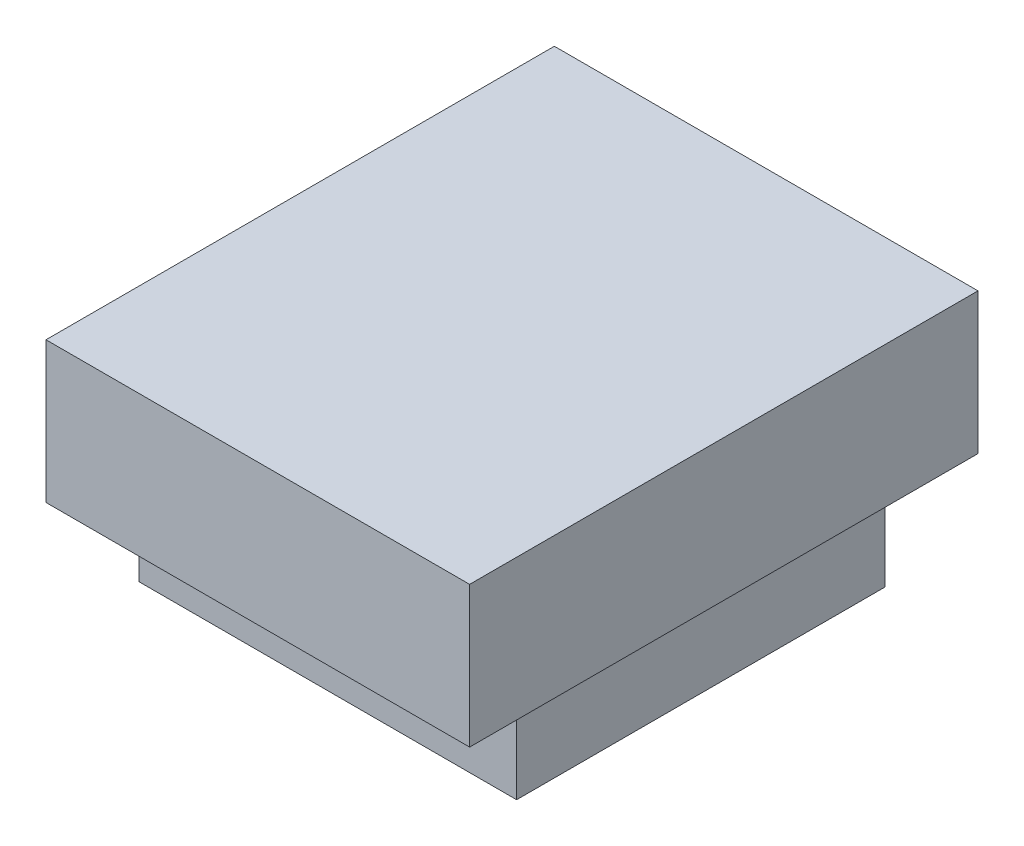
SolidWorks part; units mm, degrees
ref_plane "Front Plane" through (0, 0, 0) normal (0, 0, 1) x (1, 0, 0)
ref_plane "Top Plane" through (0, 0, 0) normal (0, 1, 0) x (1, 0, 0)
ref_plane "Right Plane" through (0, 0, 0) normal (1, 0, 0) x (0, 0, -1)
sketch "Sketch1" plane through (0, 0, 0) normal (0, 1, 0) x (1, 0, 0)
  line L1 (-102.5, -100) -> (102.5, -100)
  line L2 (-102.5, -100) -> (-102.5, 100)
  line L3 (-102.5, 100) -> (102.5, 100)
  line L4 (102.5, -100) -> (102.5, 100)
  line L5 (-102.5, -100) -> (102.5, 100) construction
  line L6 (-102.5, 100) -> (102.5, -100) construction
  line L7 (-115, -138) -> (115, -138)
  line L8 (-115, -138) -> (-115, 138)
  line L9 (-115, 138) -> (115, 138)
  line L10 (115, -138) -> (115, 138)
  line L11 (-115, -138) -> (115, 138) construction
  line L12 (-115, 138) -> (115, -138) construction
  point P0 (0, 0)
  point P6 (0, 0)
  dimension "D1" = 205
  dimension "D2" = 200
  dimension "D3" = 230
  dimension "D4" = 276
extrude "Boss-Extrude1" add sketch "Sketch1" along normal blind 50 contours L1 L4 L3 L2 region at (0, 0, 0)
extrude "Boss-Extrude2" add sketch "Sketch1<3>" along normal blind 76.5302 from surface contours L10 L9 L8 L7 starting at face at (0, 50, 0)
sketch "Sketch1<3>" plane through (0, 0, 0) normal (0, 1, 0) x (1, 0, 0) same geometry as "Sketch1"
